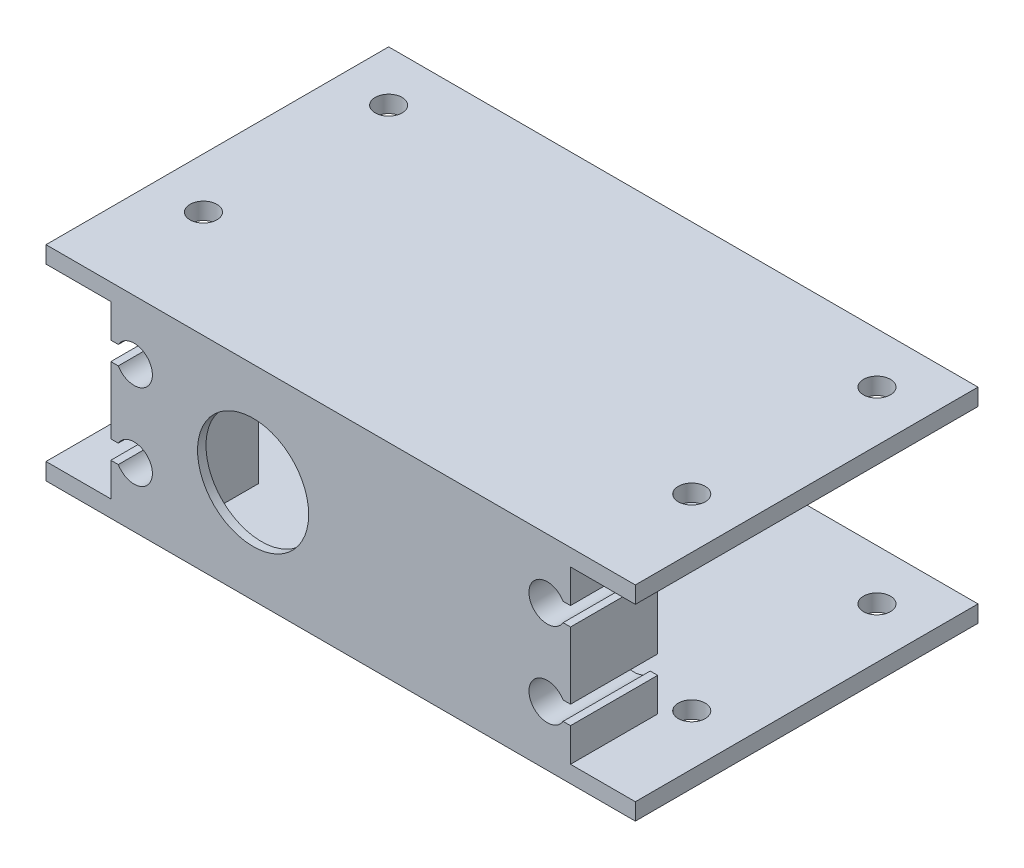
SolidWorks part; units mm, degrees
ref_plane "Front Plane" through (0, 0, 0) normal (0, 0, 1) x (1, 0, 0)
ref_plane "Top Plane" through (0, 0, 0) normal (0, 1, 0) x (1, 0, 0)
ref_plane "Right Plane" through (0, 0, 0) normal (1, 0, 0) x (0, 0, -1)
sketch "Sketch1" plane through (0, 0, 0) normal (0, 0, 1) x (1, 0, 0)
  line L1 (0, 0) -> (40.2, 0)
  line L2 (0, 0) -> (0, 24.3)
  line L3 (0, 24.3) -> (40.2, 24.3)
  line L4 (40.2, 0) -> (40.2, 24.3)
  line L8 (0, 22.3) -> (40.2, 22.3)
  line L9 (40.2, 22.3) -> (40.2, 2)
  line L10 (40.2, 2) -> (0, 2)
  line L11 (0, 2) -> (0, 22.3)
  line L12 (0.1, 2) -> (40.1, 2)
  circle A0 centre (9.7, 12.15) radius 6.6
  point P11 (3.1, 12.15)
  point P13 (0, 12.15)
  point P16 (20.1, 2)
  dimension "D5" = 13.2
  dimension "D1" = 24.3
  dimension "D2" = 40.2
  dimension "D3" = 2
  dimension "D4" = 2
  dimension "D6" = 3
  dimension "D7" = 40
extrude "Boss-Extrude1" add sketch "Sketch1" along normal blind 40.7 contours L2 L8 L4 L3 | L4 L10 L2 L1 region at (20.1, 1, 0) region at (20.1, 23.3, 0)
extrude "Boss-Extrude3" add sketch "Sketch1<3>" against normal blind 1 from surface contours L10 L4 L8 L2 A0 region at (22.1954, 12.15, 0) starting at face at (20.1, 23.3, 40.7)
sketch "Sketch1<3>" plane through (0, 0, 0) normal (0, 0, 1) x (1, 0, 0) same geometry as "Sketch1"
sketch "Sketch3" plane through (0, -15.7, 39.7) normal (0, 0, -1) x (1, 0, 0)
  line L0 (-4.4387, -24.95) -> (-4.4387, -30.75) construction
  line L1 (0, -40) -> (-7.2, -40)
  line L2 (0, -40) -> (0, -15.7)
  line L3 (0, -15.7) -> (-7.2, -15.7)
  line L4 (-7.2, -40) -> (-7.2, -15.7)
  line L5 (-7.2, -23.875) -> (-6.315, -23.875)
  line L6 (-7.2, -21.675) -> (-6.315, -21.675)
  line L7 (-7.2, -21.675) -> (-7.2, -23.875)
  line L8 (-6.315, -34.025) -> (-7.2, -34.025)
  line L9 (-7.2, -34.025) -> (-7.2, -31.825)
  line L10 (-7.2, -31.825) -> (-6.315, -31.825)
  line L11 (0, -38) -> (0, -17.7) construction
  line L12 (0.1, -40) -> (40.1, -40)
  line L13 (0, -40) -> (40.2, -40) construction
  arc A0 (-6.315, -23.875) -> (-6.315, -21.675) centre (-4.4387, -22.775) ccw
  arc A1 (-6.315, -34.025) -> (-6.315, -31.825) centre (-4.4387, -32.925) ccw
  point P13 (-7.2, -27.85)
  point P14 (-4.4387, -27.85)
  point P21 (0, -27.85)
  point P23 (0, -27.85)
  point P29 (20.1, -40)
  point P30 (20.1, -40)
  dimension "D2" = 4.35
  dimension "D1" = 7.3
  dimension "D3" = 5.8
  dimension "D4" = 0.885
  dimension "D5" = 2.2
  dimension "D6" = 40
extrude "Boss-Extrude2" add sketch "Sketch3" along normal blind 9.35 and the other way up to surface (1 mm away) contours A0 L0 A1 L8 L4 L1 L3 L6 | L0 A0 L5 L4 L10 A1 region at (-2.959, 12.15, 39.7) region at (-5.9161, 12.15, 39.7) other way up to face at (20.1, 12.15, 40.7)
ref_plane "Plane1" through (20.1, 0, 0) normal (1, 0, 0) x (0, 0, -1)
mirror "Mirror1" about plane through (20.1, 0, 0) normal (1, 0, 0) of "Boss-Extrude2"
sketch "Sketch4" plane through (0, 24.3, 0) normal (0, 1, 0) x (1, 0, 0)
  line L0 (0, 0) -> (40.2, 0) construction
  line L1 (-14.9, 0) -> (55.1, 0)
  line L2 (-14.9, 0) -> (-14.9, -40.7)
  line L3 (-14.9, -40.7) -> (55.1, -40.7)
  line L4 (55.1, 0) -> (55.1, -40.7)
  line L5 (-7.2, -40.7) -> (47.4, -40.7) construction
  line L6 (-8.9, -6) -> (49.1, -6) construction
  line L7 (-8.9, -6) -> (-8.9, -28) construction
  circle A0 centre (-8.9, -6) radius 1.6
  circle A1 centre (49.1, -6) radius 1.6
  circle A2 centre (49.1, -28) radius 1.6
  circle A3 centre (-8.9, -28) radius 1.6
  point P6 (20.1, 0)
  line M11 (0, 0) -> (0, -30.35)
  line M12 (0, -30.35) -> (-7.2, -30.35)
  line M13 (-7.2, -30.35) -> (-7.2, -40.7)
  line M15 (47.4, -40.7) -> (47.4, -30.35)
  line M16 (47.4, -30.35) -> (40.2, -30.35)
  line M17 (40.2, -30.35) -> (40.2, 0)
  dimension "D2" = 3.2
  dimension "D1" = 70
  dimension "D3" = 6
  dimension "D4" = 6
  dimension "D7" = 58
  dimension "D8" = 22
  dimension "D5" = 2
  dimension "D6" = 2
extrude "Boss-Extrude4" add sketch "Sketch4" against normal blind 2 contours L2 L3 L1 A3 A0 M13 M12 M11 | L4 L1 L3 A2 A1 M17 M16 M15 region at (-7.961, 24.3, 18.2622) region at (48.161, 24.3, 18.2622)
extrude "Boss-Extrude5" add sketch "Sketch4<3>" along normal blind 2 from surface starting at face at (20.1, 0, 25.35)
sketch "Sketch4<3>" plane through (0, 24.3, 0) normal (0, 1, 0) x (1, 0, 0) same geometry as "Sketch4"
